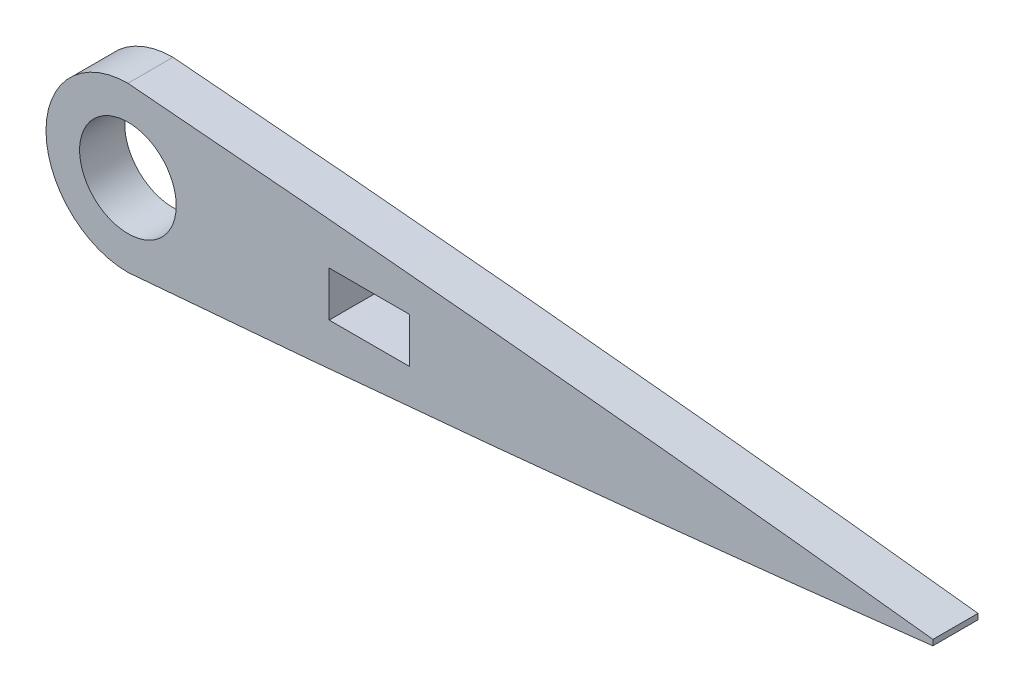
SolidWorks part; units mm, degrees
material "Фанера"
ref_plane "Спереди" through (0, 0, 0) normal (0, 0, 1) x (1, 0, 0)
ref_plane "Сверху" through (0, 0, 0) normal (0, 1, 0) x (1, 0, 0)
ref_plane "Справа" through (0, 0, 0) normal (1, 0, 0) x (0, 0, -1)
curve "Кривая1"
  spline degree 3 poles (200, 0.1747, 0) (199.6007, 0.2213, 0) (198.4854, 0.3514, 0) (196.462, 0.5838, 0) (193.7856, 0.8861, 0) (190.6579, 1.2319, 0) (187.1764, 1.6078, 0) (183.4067, 2.0045, 0) (179.3984, 2.4149, 0) (175.1909, 2.8335, 0) (170.8176, 3.2558, 0) (166.3067, 3.6778, 0) (161.6831, 4.0963, 0) (156.9692, 4.5083, 0) (152.1848, 4.9111, 0) (147.3484, 5.3022, 0) (142.4768, 5.6794, 0) (137.5855, 6.0402, 0) (132.6892, 6.3824, 0) (127.8016, 6.7038, 0) (122.9356, 7.0023, 0) (118.1034, 7.2757, 0) (113.3167, 7.5219, 0) (108.5864, 7.7388, 0) (103.9232, 7.9245, 0) (99.3373, 8.0772, 0) (94.8383, 8.1952, 0) (90.4357, 8.2769, 0) (86.1385, 8.321, 0) (81.9555, 8.3264, 0) (77.8951, 8.2921, 0) (73.9656, 8.2177, 0) (70.1749, 8.1027, 0) (66.5308, 7.947, 0) (63.0408, 7.751, 0) (59.7122, 7.515, 0) (56.5522, 7.2398, 0) (53.5677, 6.9266, 0) (50.7656, 6.5764, 0) (48.1524, 6.1907, 0) (45.7346, 5.7713, 0) (43.5185, 5.3197, 0) (41.5102, 4.8379, 0) (39.7154, 4.3278, 0) (38.1397, 3.791, 0) (36.7878, 3.2294, 0) (35.6652, 2.6441, 0) (34.771, 2.0345, 0) (34.119, 1.3968, 0) (33.6837, 0.7187, 0) (33.627, 0.2317, 0) (33.6, 0, 0) knots 0 0 0 0 0.007145 0.019956 0.036196 0.055011 0.075879 0.098429 0.122376 0.147488 0.173572 0.20046 0.228005 0.256076 0.284555 0.313333 0.34231 0.371393 0.400496 0.429538 0.458442 0.487136 0.515552 0.543624 0.57129 0.598491 0.62517 0.651272 0.676746 0.701542 0.725611 0.748908 0.771388 0.793008 0.813728 0.833508 0.85231 0.870097 0.886836 0.902493 0.917037 0.930441 0.94268 0.953734 0.96359 0.972247 0.979722 0.986065 0.991385 0.995901 1 1 1 1
curve "Кривая2"
  spline degree 3 poles (33.6, 0, 0) (33.627, -0.2317, 0) (33.6837, -0.7187, 0) (34.119, -1.3968, 0) (34.771, -2.0345, 0) (35.6652, -2.6441, 0) (36.7878, -3.2294, 0) (38.1397, -3.791, 0) (39.7154, -4.3278, 0) (41.5102, -4.8379, 0) (43.5185, -5.3197, 0) (45.7346, -5.7713, 0) (48.1524, -6.1907, 0) (50.7656, -6.5764, 0) (53.5677, -6.9266, 0) (56.5522, -7.2398, 0) (59.7122, -7.515, 0) (63.0408, -7.751, 0) (66.5308, -7.947, 0) (70.1749, -8.1027, 0) (73.9656, -8.2177, 0) (77.8951, -8.2921, 0) (81.9555, -8.3264, 0) (86.1385, -8.321, 0) (90.4357, -8.2769, 0) (94.8383, -8.1952, 0) (99.3373, -8.0772, 0) (103.9232, -7.9245, 0) (108.5864, -7.7388, 0) (113.3167, -7.5219, 0) (118.1034, -7.2757, 0) (122.9356, -7.0023, 0) (127.8016, -6.7038, 0) (132.6892, -6.3824, 0) (137.5855, -6.0402, 0) (142.4768, -5.6794, 0) (147.3484, -5.3022, 0) (152.1848, -4.9111, 0) (156.9692, -4.5083, 0) (161.6831, -4.0963, 0) (166.3067, -3.6778, 0) (170.8176, -3.2558, 0) (175.1909, -2.8335, 0) (179.3984, -2.4149, 0) (183.4067, -2.0045, 0) (187.1764, -1.6078, 0) (190.6579, -1.2319, 0) (193.7856, -0.8861, 0) (196.462, -0.5838, 0) (198.4854, -0.3514, 0) (199.6007, -0.2213, 0) (200, -0.1747, 0) knots 0 0 0 0 0.004099 0.008615 0.013935 0.020278 0.027753 0.03641 0.046266 0.05732 0.069559 0.082963 0.097507 0.113164 0.129903 0.14769 0.166492 0.186272 0.206992 0.228612 0.251092 0.274389 0.298458 0.323254 0.348728 0.37483 0.401509 0.42871 0.456376 0.484448 0.512864 0.541558 0.570462 0.599504 0.628607 0.65769 0.686667 0.715445 0.743924 0.771995 0.79954 0.826428 0.852512 0.877624 0.901571 0.924121 0.944989 0.963804 0.980044 0.992855 1 1 1 1
sketch "Эскиз1" plane through (0, 0, 0) normal (0, 0, 1) x (1, 0, 0)
  line L0 (200, 0.1747) -> (200, -0.1747)
  line L1 (97.6, -8.1212) -> (97.6, -5.0393)
  line L2 (97.6, -5.0393) -> (100.4, -5.0393)
  line L3 (100.4, -5.0393) -> (100.4, -8.0393)
  line L4 (124, 6.9352) -> (124, 3.7634)
  line L5 (124, 3.7634) -> (126.8, 3.7634)
  line L6 (126.8, 3.7634) -> (126.8, 6.7634)
  line L7 (63.6, 7.7774) -> (63.6, 4.7774)
  line L8 (63.6, 4.7774) -> (66.4, 4.7774)
  line L9 (66.4, 4.7774) -> (66.4, 7.9325)
  line L11 (162.5, -1.4) -> (167.5, -1.4)
  line L12 (162.5, -1.4) -> (162.5, 1.4)
  line L13 (162.5, 1.4) -> (167.5, 1.4)
  line L14 (167.5, -1.4) -> (167.5, 1.4)
  line L15 (162.5, -1.4) -> (167.5, 1.4) construction
  line L16 (162.5, 1.4) -> (167.5, -1.4) construction
  circle A0 centre (109, 0) radius 4
  circle A1 centre (55, 0) radius 4
  arc A2 (150, 5.0871) -> (150, -5.0871) centre (150, 0) ccw
  arc A3 (142.8797, 5.6459) -> (142.8797, -5.6459) centre (150, 0) ccw
  circle A5 centre (150, 0) radius 3
  spline S0 degree 3 poles (-2831.395, -885.4831) (104.8143, 41.236) (28.6845, 7.0703) (34.119, -1.3968) (34.771, -2.0345) (35.6652, -2.6441) (36.7878, -3.2294) (38.1397, -3.791) (39.7154, -4.3278) (41.5102, -4.8379) (43.5185, -5.3197) (45.7346, -5.7713) (48.1524, -6.1907) (50.7656, -6.5764) (53.5677, -6.9266) (56.5522, -7.2398) (59.7122, -7.515) (63.0408, -7.751) (66.5308, -7.947) (70.1749, -8.1027) (73.9656, -8.2177) (77.8951, -8.2921) (81.9555, -8.3264) (86.1385, -8.321) (90.4357, -8.2769) (94.8383, -8.1952) (99.3373, -8.0772) (103.9232, -7.9245) (108.5864, -7.7388) (113.3167, -7.5219) (118.1034, -7.2757) (122.9356, -7.0023) (127.8016, -6.7038) (132.6892, -6.3824) (137.5855, -6.0402) (142.4768, -5.6794) (147.3484, -5.3022) (152.1848, -4.9111) (156.9692, -4.5083) (161.6831, -4.0963) (167.7684, -3.5455) (173.6854, -2.9833) (179.3984, -2.4149) (183.4067, -2.0045) (187.1764, -1.6078) (190.6579, -1.2319) (193.7856, -0.8861) (196.462, -0.5838) (290.0824, 10.1714) (381.2595, 34.0447) (818.4439, -2928.0188) knots -0.160047 -0.160047 -0.160047 -0.160047 0.004099 0.008615 0.013935 0.020278 0.027753 0.03641 0.046266 0.05732 0.069559 0.082963 0.097507 0.113164 0.129903 0.14769 0.166492 0.186272 0.206992 0.228612 0.251092 0.274389 0.298458 0.323254 0.348728 0.37483 0.401509 0.42871 0.456376 0.484448 0.512864 0.541558 0.570462 0.599504 0.628607 0.65769 0.686667 0.715445 0.743924 0.771995 0.79954 0.852512 0.877624 0.901571 0.924121 0.944989 0.963804 0.980044 0.992855 2.638559 2.638559 2.638559 2.638559 only from (33.6, 0) to (200, -0.1747) construction
  spline S1 degree 3 poles (961.5333, 3917.5463) (399.4787, -38.9514) (299.3532, -11.2364) (196.462, 0.5838) (193.7856, 0.8861) (190.6579, 1.2319) (187.1764, 1.6078) (183.4067, 2.0045) (179.3984, 2.4149) (173.6854, 2.9833) (167.7684, 3.5455) (161.6831, 4.0963) (156.9692, 4.5083) (152.1848, 4.9111) (147.3484, 5.3022) (142.4768, 5.6794) (137.5855, 6.0402) (132.6892, 6.3824) (127.8016, 6.7038) (122.9356, 7.0023) (118.1034, 7.2757) (113.3167, 7.5219) (108.5864, 7.7388) (103.9232, 7.9245) (99.3373, 8.0772) (94.8383, 8.1952) (90.4357, 8.2769) (86.1385, 8.321) (81.9555, 8.3264) (77.8951, 8.2921) (73.9656, 8.2177) (70.1749, 8.1027) (66.5308, 7.947) (63.0408, 7.751) (59.7122, 7.515) (56.5522, 7.2398) (53.5677, 6.9266) (50.7656, 6.5764) (48.1524, 6.1907) (45.7346, 5.7713) (43.5185, 5.3197) (41.5102, 4.8379) (39.7154, 4.3278) (38.1397, 3.791) (36.7878, 3.2294) (35.6652, 2.6441) (34.771, 2.0345) (34.119, 1.3968) (28.1816, -7.8538) (120.0893, -47.9948) (-3785.1012, 1186.7838) knots -1.804403 -1.804403 -1.804403 -1.804403 0.007145 0.019956 0.036196 0.055011 0.075879 0.098429 0.122376 0.147488 0.20046 0.228005 0.256076 0.284555 0.313333 0.34231 0.371393 0.400496 0.429538 0.458442 0.487136 0.515552 0.543624 0.57129 0.598491 0.62517 0.651272 0.676746 0.701542 0.725611 0.748908 0.771388 0.793008 0.813728 0.833508 0.85231 0.870097 0.886836 0.902493 0.917037 0.930441 0.94268 0.953734 0.96359 0.972247 0.979722 0.986065 0.991385 0.995901 1.176146 1.176146 1.176146 1.176146 only from (200, 0.1747) to (33.6, 0) construction
  spline S2 degree 3 poles (33.6, 0) (33.627, -0.2317) (33.6837, -0.7187) (34.119, -1.3968) (34.771, -2.0345) (35.6652, -2.6441) (36.7878, -3.2294) (38.1397, -3.791) (39.7154, -4.3278) (41.5102, -4.8379) (43.5185, -5.3197) (45.7346, -5.7713) (48.1524, -6.1907) (50.7656, -6.5764) (53.5677, -6.9266) (56.5522, -7.2398) (59.7122, -7.515) (63.0408, -7.751) (66.5308, -7.947) (70.1749, -8.1027) (73.9656, -8.2177) (77.8951, -8.2921) (81.9555, -8.3264) (86.1385, -8.321) (90.4357, -8.2769) (94.2689, -8.2058) (96.6686, -8.1464) (97.6, -8.1212) knots 0 0 0 0 0.004099 0.008615 0.013935 0.020278 0.027753 0.03641 0.046266 0.05732 0.069559 0.082963 0.097507 0.113164 0.129903 0.14769 0.166492 0.186272 0.206992 0.228612 0.251092 0.274389 0.298458 0.323254 0.348728 0.37483 0.391389 0.391389 0.391389 0.391389
  spline S3 degree 3 poles (200, 0.1747) (199.6007, 0.2213) (198.4854, 0.3514) (196.462, 0.5838) (193.7856, 0.8861) (190.6579, 1.2319) (187.1764, 1.6078) (183.4067, 2.0045) (179.3984, 2.4149) (173.6854, 2.9833) (167.7684, 3.5455) (161.6831, 4.0963) (156.9692, 4.5083) (152.1848, 4.9111) (147.3484, 5.3022) (142.4768, 5.6794) (137.5855, 6.0402) (132.6892, 6.3824) (129.0934, 6.6189) (127.1312, 6.7427) (126.8, 6.7634) knots 0 0 0 0 0.007145 0.019956 0.036196 0.055011 0.075879 0.098429 0.122376 0.147488 0.20046 0.228005 0.256076 0.284555 0.313333 0.34231 0.371393 0.400496 0.429538 0.435436 0.435436 0.435436 0.435436
  spline S4 degree 3 poles (124, 6.9352) (123.6412, 6.9567) (121.6707, 7.0739) (118.1034, 7.2757) (113.3167, 7.5219) (108.5864, 7.7388) (103.9232, 7.9245) (99.3373, 8.0772) (94.8383, 8.1952) (90.4357, 8.2769) (86.1385, 8.321) (81.9555, 8.3264) (77.8951, 8.2921) (73.9656, 8.2177) (70.1749, 8.1027) (67.6688, 7.9956) (66.4269, 7.9339) (66.4, 7.9325) knots 0.452054 0.452054 0.452054 0.452054 0.458442 0.487136 0.515552 0.543624 0.57129 0.598491 0.62517 0.651272 0.676746 0.701542 0.725611 0.748908 0.771388 0.793008 0.793486 0.793486 0.793486 0.793486
  spline S5 degree 3 poles (100.4, -8.0393) (101.5657, -8.0027) (104.2872, -7.91) (108.5864, -7.7388) (113.3167, -7.5219) (118.1034, -7.2757) (122.9356, -7.0023) (127.8016, -6.7038) (132.6892, -6.3824) (137.5855, -6.0402) (142.4768, -5.6794) (147.3484, -5.3022) (152.1848, -4.9111) (156.9692, -4.5083) (161.6831, -4.0963) (167.7684, -3.5455) (173.6854, -2.9833) (179.3984, -2.4149) (183.4067, -2.0045) (187.1764, -1.6078) (190.6579, -1.2319) (193.7856, -0.8861) (196.462, -0.5838) (198.4854, -0.3514) (199.6007, -0.2213) (200, -0.1747) knots 0.407983 0.407983 0.407983 0.407983 0.42871 0.456376 0.484448 0.512864 0.541558 0.570462 0.599504 0.628607 0.65769 0.686667 0.715445 0.743924 0.771995 0.79954 0.852512 0.877624 0.901571 0.924121 0.944989 0.963804 0.980044 0.992855 1 1 1 1
  spline S6 degree 3 poles (63.6, 7.7774) (63.3962, 7.765) (62.0815, 7.683) (59.7122, 7.515) (56.5522, 7.2398) (53.5677, 6.9266) (50.7656, 6.5764) (48.1524, 6.1907) (45.7346, 5.7713) (43.5185, 5.3197) (41.5102, 4.8379) (39.7154, 4.3278) (38.1397, 3.791) (36.7878, 3.2294) (35.6652, 2.6441) (34.771, 2.0345) (34.119, 1.3968) (33.6837, 0.7187) (33.627, 0.2317) (33.6, 0) knots 0.810099 0.810099 0.810099 0.810099 0.813728 0.833508 0.85231 0.870097 0.886836 0.902493 0.917037 0.930441 0.94268 0.953734 0.96359 0.972247 0.979722 0.986065 0.991385 0.995901 1 1 1 1
  point P14 (99, -5.0393)
  point P20 (65, 4.7774)
  point P27 (165, 0)
  dimension "D1" = 8
  dimension "D2" = 8
  dimension "D16" = 5.0871
  dimension "D17" = 9.0871
  dimension "D18" = 6
  dimension "D3" = 75.4
  dimension "D4" = 21.4
  dimension "D5" = 2.8
  dimension "D6" = 2.8
  dimension "D7" = 10
  dimension "D8" = 15
  dimension "D9" = 3
  dimension "D10" = 3
  dimension "D11" = 2.8
  dimension "D12" = 10
  dimension "D13" = 3
  dimension "D14" = 116.4
  dimension "D15" = 10.1742
  dimension "D19" = 2.8
  dimension "D20" = 5
  dimension "D21" = 15
  dimension "D22" = 0
extrude "Бобышка-Вытянуть1" add sketch "Эскиз1" along normal mid plane 2.8 contours A2 S5 L0 S3 A5 region at (199.4398, 0, 0)
equation "\"D3@Эскиз1\"=109-33.6"
equation "\"D16@Эскиз1\"=\"D15@Эскиз1\"/2"
equation "\"D17@Эскиз1\"=\"D16@Эскиз1\"+4"
